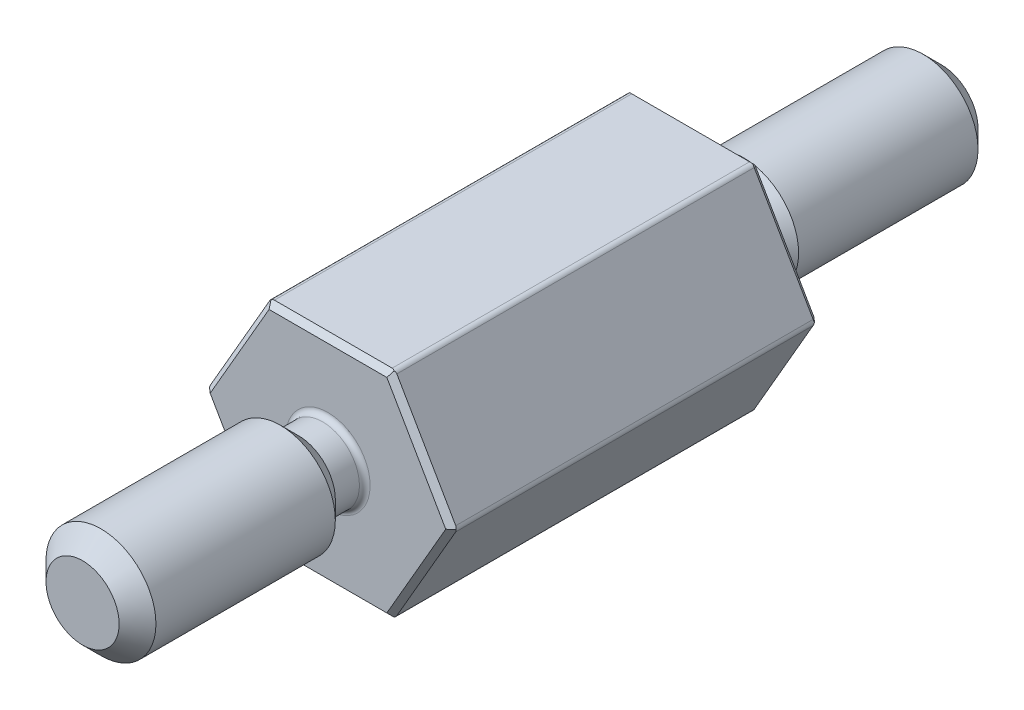
SolidWorks part; units mm, degrees
ref_plane "Front Plane" through (0, 0, 0) normal (0, 0, 1) x (1, 0, 0)
ref_plane "Top Plane" through (0, 0, 0) normal (0, 1, 0) x (1, 0, 0)
ref_plane "Right Plane" through (0, 0, 0) normal (1, 0, 0) x (0, 0, -1)
sketch "Sketch1" plane through (0, 0, 0) normal (0, 0, 1) x (1, 0, 0)
  line L0 (0, 0) -> (3.2079, 0) construction
  line L1 (1.604, 2.7781) -> (-1.604, 2.7781)
  line L2 (-1.604, 2.7781) -> (-3.2079, 0)
  line L3 (-3.2079, 0) -> (-1.604, -2.7781)
  line L4 (-1.604, -2.7781) -> (1.604, -2.7781)
  line L5 (1.604, -2.7781) -> (3.2079, 0)
  line L6 (3.2079, 0) -> (1.604, 2.7781)
  circle A0 centre (0, 0) radius 2.7781 construction
sketch "Sketch2" plane through (0, 0, 0) normal (1, 0, 0) x (0, 0, -1)
  line L0 (-4.7625, 2.7781) -> (4.7625, 2.7781) construction
  line L1 (-11.1125, 0) -> (-4.7625, 0) construction
  line L2 (-11.1125, 1.4224) -> (-11.1125, -1.4224) construction
  line L3 (-11.7078, 1.4911) -> (-11.0728, 1.4911) construction
  line L4 (-11.0728, 1.4911) -> (-11.3903, 0.9412) construction
  line L5 (-11.3903, 0.9412) -> (-11.7078, 1.4911) construction
  line L6 (-11.6681, 1.4224) -> (-11.1125, 1.4224) construction
  line L7 (-11.43, 1.01) -> (-11.3506, 1.01) construction
  line L8 (-11.3903, 1.01) -> (-11.3903, 0.9412) construction
  line L9 (-11.3903, 1.4224) -> (-11.3903, 1.4911) construction
  line L10 (4.7625, 0) -> (11.1125, 0) construction
  line L11 (-4.7625, 0.9525) -> (-5.5245, 0.9525) construction
  line L12 (-11.1125, 0.9144) -> (-10.6045, 1.4224) construction
  point P2 (0, 2.7781)
  point P20 (9.7631, -1.4224)
  dimension "Thread Length_1" = 6.35
sketch "Sketch3" plane through (0, 0, 0) normal (1, 0, 0) x (0, 0, -1)
  line L0 (11.1125, 0) -> (-11.1125, 0)
  line L1 (-11.1125, 0) -> (-11.1125, 0.9461)
  line L2 (-11.1125, 1.4224) -> (-11.1125, -1.4224) construction
  line L3 (-11.1125, 0.9461) -> (-10.6363, 1.4224)
  line L4 (-10.6363, 1.4224) -> (-5.9944, 1.4224)
  line L5 (-4.7625, 0.9525) -> (-4.7625, 2.7781)
  line L6 (-4.7625, 2.7781) -> (4.7625, 2.7781)
  line L7 (4.7625, 2.7781) -> (4.7625, 0.9525)
  line L8 (5.9944, 1.4224) -> (10.6362, 1.4224)
  line L9 (10.6362, 1.4224) -> (11.1125, 0.9462)
  line L10 (11.1125, 0.9462) -> (11.1125, 0)
  line L11 (-5.9944, 1.4224) -> (-5.5245, 0.9525)
  line L12 (-5.5245, 0.9525) -> (-4.7625, 0.9525)
  line L13 (5.9944, 1.4224) -> (5.5245, 0.9525)
  line L14 (5.5245, 0.9525) -> (4.7625, 0.9525)
  dimension "D1" = 0.4763
  dimension "D2" = 45
  dimension "D3" = 45
revolve "Revolve1" add sketch "Sketch3" angle 360 about L1
sketch "Sketch4" plane through (0, 0, 0) normal (0, 0, 1) x (1, 0, 0)
  line L1 (-3.2079, 0) -> (-1.604, -2.7781)
  line L2 (-1.604, -2.7781) -> (1.604, -2.7781)
  line L3 (1.604, -2.7781) -> (3.2079, 0)
  line L4 (3.2079, 0) -> (1.604, 2.7781)
  line L5 (1.604, 2.7781) -> (-1.604, 2.7781)
  line L6 (-1.604, 2.7781) -> (-3.2079, 0)
  line L7 (1.604, 2.7781) -> (-1.604, 2.7781) construction
  circle A0 centre (0, 0) radius 2.7781 construction
  circle A1 centre (0, 0) radius 2.7781 construction
extrude "Boss-Extrude1" add sketch "Sketch4" against normal up to vertex (4.7625 mm away) and the other way up to vertex (4.7625 mm away) up to point (0, 2.7781, -4.7625) other way up to point (0, 2.7781, 4.7625)
chamfer "Chamfer1" distance 0.1389 angle 45 12 edges at (-2.4059, 1.3891, -4.7625) (-2.4059, -1.3891, -4.7625) (0, -2.7781, -4.7625) (2.4059, -1.3891, -4.7625) (2.4059, 1.3891, -4.7625) (0, 2.7781, -4.7625) (0, -2.7781, 4.7625) (-2.4059, -1.3891, 4.7625) (-2.4059, 1.3891, 4.7625) (0, 2.7781, 4.7625) (2.4059, 1.3891, 4.7625) (2.4059, -1.3891, 4.7625)
fillet "Fillet1" radius 0.1389 8 edges at (-3.2079, 0, 0) (-1.604, -2.7781, 0) (1.604, -2.7781, 0) (3.2079, 0, 0) (-1.604, 2.7781, 0) (1.604, 2.7781, 0) (0.9525, 0, -4.7625) (0.9525, 0, 4.7625)
sketch "Sketch5" plane through (0, 0, 11.1125) normal (0, 0, 1) x (1, 0, 0)
  circle A0 centre (0, 0) radius 1.4224
curve "Helix/Spiral1" [suppressed] pitch 0.635 height 6.0985 turns 9.604
sketch "Sketch6" plane through (0, 0, 0) normal (1, 0, 0) x (0, 0, -1)
  line L0 (-11.43, 1.01) -> (-11.3506, 1.01)
  line L1 (-11.3506, 1.01) -> (-11.0927, 1.4568)
  line L2 (-11.0728, 1.4911) -> (-11.3903, 0.9412) construction
  line L3 (-11.0927, 1.4568) -> (-11.688, 1.4568)
  line L4 (-11.3903, 0.9412) -> (-11.7078, 1.4911) construction
  line L5 (-11.688, 1.4568) -> (-11.43, 1.01)
  line L6 (-11.3903, 1.4224) -> (-11.3903, 1.4911) construction
  point P12 (-11.3903, 1.4568)
sweep "Cut-Sweep1" [suppressed] cut profiles "Sketch6" path "Helix/Spiral1"
pattern_circular "CirPattern1" [suppressed] count 2 over 360 about axis through (0, 0, 0) along (1, 0, 0) of bodies 107
equation "\"Pitch/8@Sketch2\" = \"Thread Pitch@Sketch2\" / 8"
equation "\"D1@Sketch3\"=\"Thread Pitch@Sketch2\" * 0.75"
equation "\"D1@Chamfer1\"=\"Hex Size@Sketch1\" * .025"
equation "\"D1@Fillet1\"=\"Hex Size@Sketch1\" * .025"
equation "\"D3@Helix/Spiral1\" = \"Thread Length_1@Sketch2\" - \"Relief Length@Sketch2\" * .33"
equation "\"D4@Helix/Spiral1\"=\"Thread Pitch@Sketch2\""
equation "\"Thread Note@Sketch2\"=\"Thread Pitch@Sketch2\" * 2.125"
